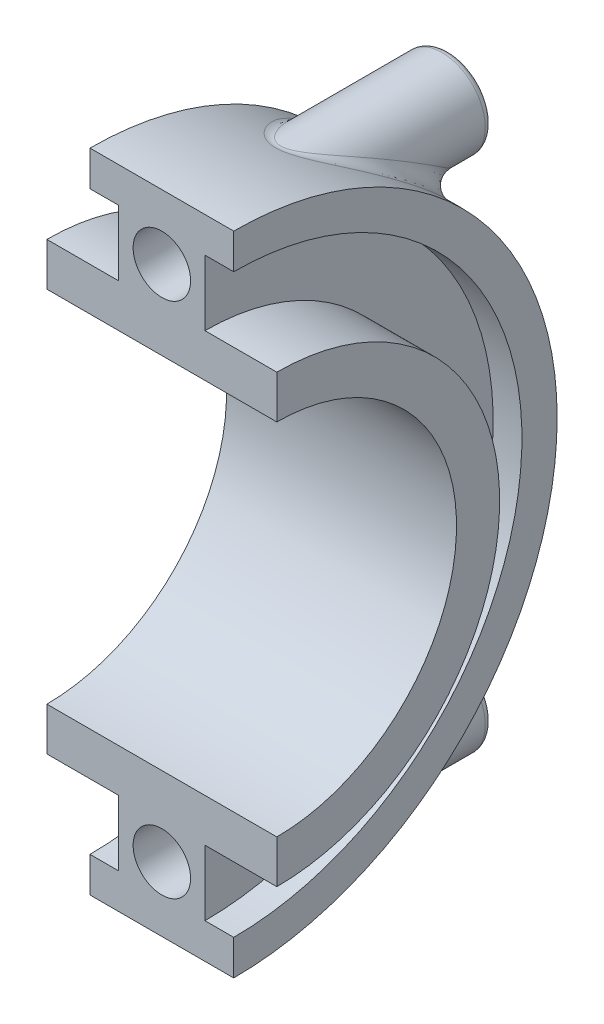
SolidWorks part; units mm, degrees
ref_plane "Front Plane" through (0, 0, 0) normal (0, 0, 1) x (1, 0, 0)
ref_plane "Top Plane" through (0, 0, 0) normal (0, 1, 0) x (1, 0, 0)
ref_plane "Right Plane" through (0, 0, 0) normal (1, 0, 0) x (0, 0, -1)
sketch "Sketch1" plane through (0, 0, 0) normal (0, 0, 1) x (1, 0, 0)
  line L0 (-10, 45) -> (-10, 40.1)
  line L1 (-10, 40.1) -> (-6, 40.1)
  line L2 (-6, 40.1) -> (-6, 31)
  line L3 (-6, 31) -> (-16, 31)
  line L4 (-16, 31) -> (-16, 25)
  line L5 (-16, 25) -> (16, 25)
  line L6 (16, 25) -> (16, 31)
  line L7 (16, 31) -> (6, 31)
  line L8 (6, 31) -> (6, 40.1)
  line L9 (6, 40.1) -> (10, 40.1)
  line L10 (10, 40.1) -> (10, 45)
  line L11 (10, 45) -> (-10, 45)
  line L12 (16.7708, 0) -> (0, 0) construction
  line L13 (0, 0) -> (0, 25) construction
  dimension "D1" = 20
  dimension "D2" = 32
  dimension "D3" = 6
  dimension "D4" = 4.9
  dimension "D5" = 20
  dimension "D6" = 12
  dimension "D7" = 25
revolve "Revolve1" add sketch "Sketch1" angle 180 about L12
sketch "Sketch2" plane through (0, 0, 0) normal (0, 0, 1) x (1, 0, 0)
  line L0 (10, 45) -> (-10, 45) construction
  circle A0 centre (0, 36) radius 6
  dimension "D1" = 12
  dimension "D2" = 9
extrude "Boss-Extrude1" add sketch "Sketch2" against normal blind 40
sketch "Sketch3" plane through (0, 0, -40) normal (0, 0, -1) x (-1, 0, 0)
  circle A0 centre (0, 36) radius 4
  dimension "D1" = 8
extrude "Cut-Extrude1" cut sketch "Sketch3" against normal through all
fillet "Fillet1" radius 2 1 edges at (-4.3409, 40.1421, -20.3375)
fillet "Fillet2" radius 1 1 edges at (6, 36, -40)
mirror "Mirror1" about plane through (0, 0, 0) normal (0, 1, 0) of "Cut-Extrude1", "Fillet2", "Fillet1", "Boss-Extrude1"
